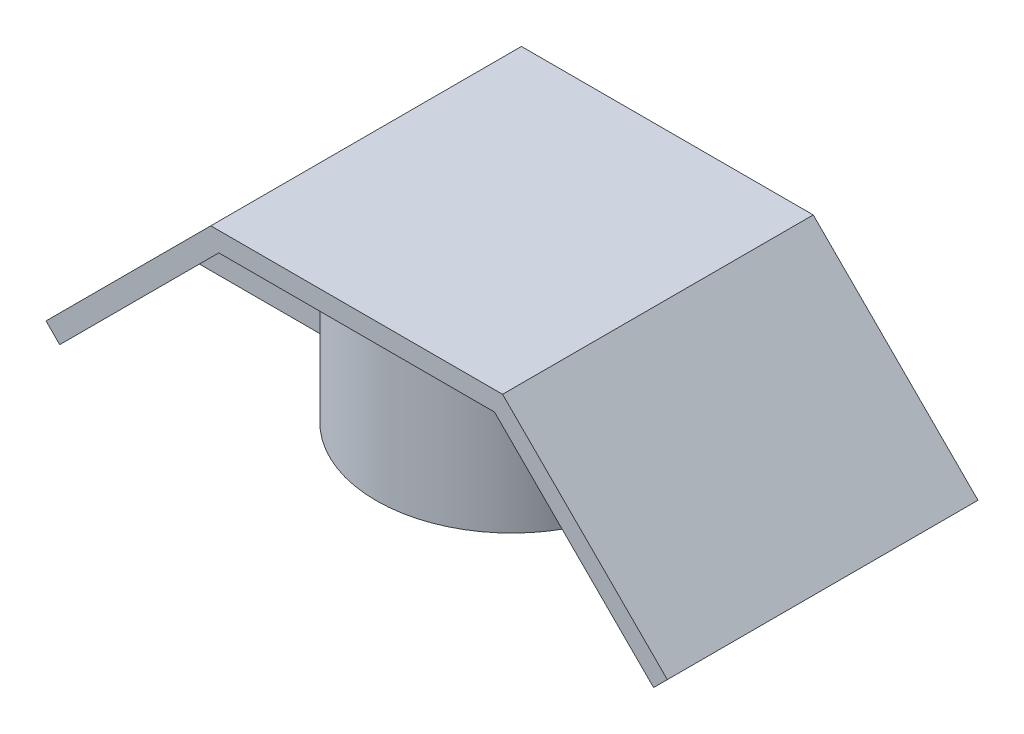
SolidWorks part; units mm, degrees
material "ABS"
ref_plane "Front Plane" through (0, 0, 0) normal (0, 0, 1) x (1, 0, 0)
ref_plane "Top Plane" through (0, 0, 0) normal (0, 1, 0) x (1, 0, 0)
ref_plane "Right Plane" through (0, 0, 0) normal (1, 0, 0) x (0, 0, -1)
sketch "Sketch1" plane through (0, 0, 0) normal (0, 0, 1) x (1, 0, 0)
  line L0 (-50.8, 0) -> (-50.8, 19.05) construction
  line L1 (-50.8, 0) -> (0, 0) construction
  line L2 (-50.8, 19.05) -> (-26.1043, 43.7457) construction
  line L3 (-26.1043, 43.7457) -> (-23.8592, 41.5006)
  line L4 (-23.8592, 41.5006) -> (-50.8, 14.5599) construction
  line L5 (0, 0) -> (0, 64.4396) construction
  line L6 (-50.8, 14.5599) -> (-23.8592, 41.5006)
  line L7 (-23.8592, 41.5006) -> (23.8592, 41.5006)
  line L8 (48.5549, 12.3148) -> (50.8, 14.5599)
  line L9 (22.5441, 38.3256) -> (-22.5441, 38.3256)
  line L10 (-22.5441, 38.3256) -> (-48.5549, 12.3148)
  line L11 (-50.8, 14.5599) -> (-48.5549, 12.3148)
  line L12 (22.5441, 38.3256) -> (48.5549, 12.3148)
  line L13 (50.8, 14.5599) -> (23.8592, 41.5006)
  circle A0 centre (-50.8, 0) radius 6.35 construction
  point P17 (0, 38.3256)
  point P18 (0, 41.5006)
  dimension "D2" = 12.7
  dimension "D1" = 50.8
  dimension "D3" = 19.05
  dimension "D4" = 135
  dimension "D5" = 3.175
  dimension "D6" = 38.1
  dimension "D7" = 3.175
  dimension "D8" = 3.175
  dimension "D9" = 38.1
extrude "Boss-Extrude1" add sketch "Sketch1" along normal blind 50.8 contours L12 region at (-36.5821, 27.2828, 0)
sketch "Sketch4" plane through (0, 38.3256, 0) normal (0, -1, 0) x (1, 0, 0)
  line L0 (0, 0) -> (0, 50.8) construction
  line L1 (22.5441, 0) -> (-22.5441, 0) construction
  line L2 (22.5441, 50.8) -> (-22.5441, 50.8) construction
  circle A0 centre (0, 25.4) radius 22.225
  point P6 (0, 25.4)
  dimension "D1" = 44.45
extrude "Boss-Extrude3" add sketch "Sketch4" along direction (0, -1, 0) on the side against the normal up to surface from offset 25.4 up to face at (0, 38.3256, 25.4)
sketch "Sketch5" plane through (0, 12.9256, 0) normal (0, -1, 0) x (1, 0, 0)
  line L0 (-48.5549, 50.8) -> (-48.5549, 0) construction
  line L1 (-48.5549, 22.225) -> (-21.997, 22.225)
  line L2 (-48.5549, 22.225) -> (-48.5549, 28.575)
  line L3 (-48.5549, 28.575) -> (-21.997, 28.575)
  line L4 (-21.997, 22.225) -> (-21.997, 28.575)
  line L5 (-22.225, 25.4) -> (0, 25.4) construction
  line L6 (0, 47.625) -> (0, 3.175) construction
  line L7 (21.997, 22.225) -> (21.997, 28.575)
  line L8 (48.5549, 22.225) -> (48.5549, 28.575)
  line L9 (48.5549, 22.225) -> (21.997, 22.225)
  line L10 (48.5549, 28.575) -> (21.997, 28.575)
  circle A0 centre (0, 25.4) radius 22.225 construction
  circle A1 centre (0, 25.4) radius 22.225 construction
  point P13 (-21.997, 25.4)
  dimension "D1" = 6.35
extrude "Boss-Extrude4" add sketch "Sketch5" against normal up to next
